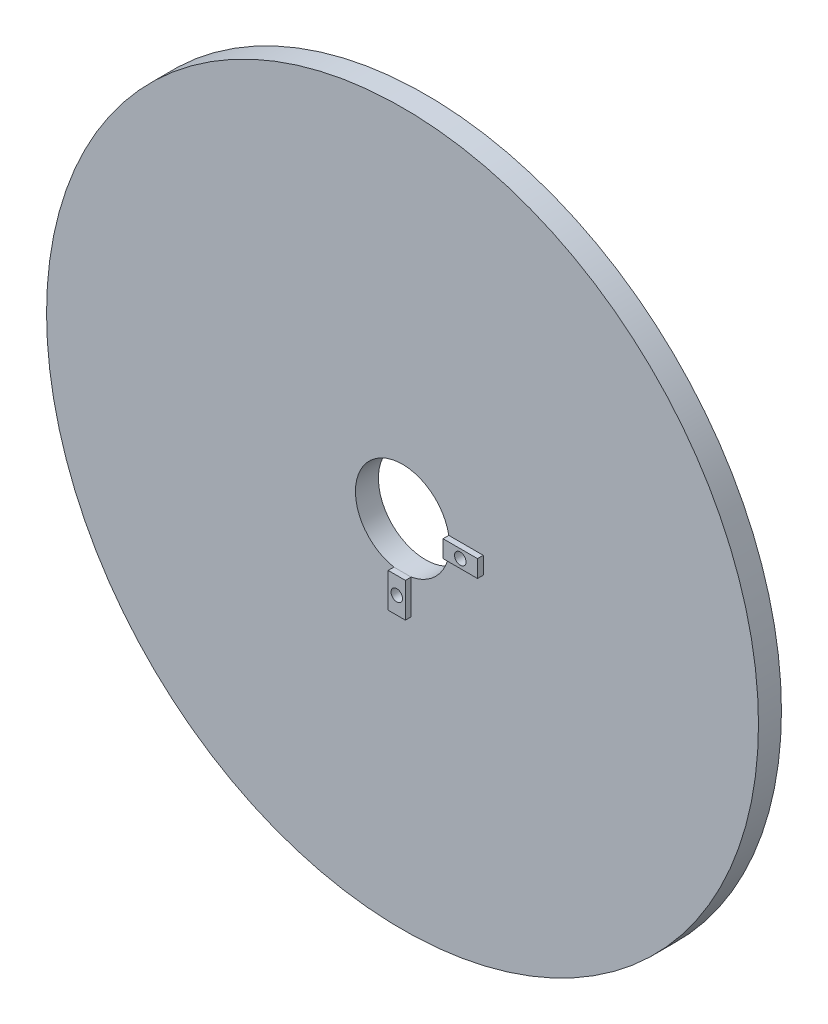
SolidWorks part; units mm, degrees
ref_plane "Ön Düzlem" through (0, 0, 0) normal (0, 0, 1) x (1, 0, 0)
ref_plane "Üst Düzlem" through (0, 0, 0) normal (0, 1, 0) x (1, 0, 0)
ref_plane "Sağ Düzlem" through (0, 0, 0) normal (1, 0, 0) x (0, 0, -1)
sketch "Çizim2" plane through (0, 0, 2) normal (0, 0, 1) x (1, 0, 0)
  circle A0 centre (0, 0) radius 2.05
  circle A1 centre (0, 0) radius 15.5
  arc A2 (5.6675, -14.9626) -> (-6.0878, -14.7966) centre (0, 0) ccw construction
  dimension "D1" = 0.5
extrude "Yükseklik-Ekstrüzyon1" add sketch "Çizim2" along normal blind 1
sketch "Çizim3" plane through (0, 0, 3) normal (0, 0, 1) x (1, 0, 0)
  line L1 (2.0154, -0.375) -> (3.5154, -0.375)
  line L2 (2.0154, -0.375) -> (2.0154, 0.375)
  line L3 (2.0154, 0.375) -> (3.5154, 0.375)
  line L4 (3.5154, -0.375) -> (3.5154, 0.375)
  line L5 (-0.375, -2.0154) -> (0.375, -2.0154)
  line L6 (-0.375, -2.0154) -> (-0.375, -3.5154)
  line L7 (-0.375, -3.5154) -> (0.375, -3.5154)
  line L8 (0.375, -2.0154) -> (0.375, -3.5154)
  circle A0 centre (0, 0) radius 2.05 construction
  circle A1 centre (2.7654, 0) radius 0.25
  circle A2 centre (0, -2.7654) radius 0.25
  point P10 (2.0154, 0)
  point P12 (0, -2.0154)
  point P18 (0.375, -2.7654)
  dimension "D3" = 0.5
  dimension "D1" = 0.75
  dimension "D2" = 1.5
extrude "Yükseklik-Ekstrüzyon2" add sketch "Çizim3" along normal blind 0.25
extrude "Kes-Ekstrüzyon1" cut sketch "Çizim3<3>" against normal through all both and the other way through all contours A2 | A1 region at (0, -2.7654, 3)
sketch "Çizim3<3>" plane through (0, 0, 3) normal (0, 0, 1) x (1, 0, 0) same geometry as "Çizim3"
